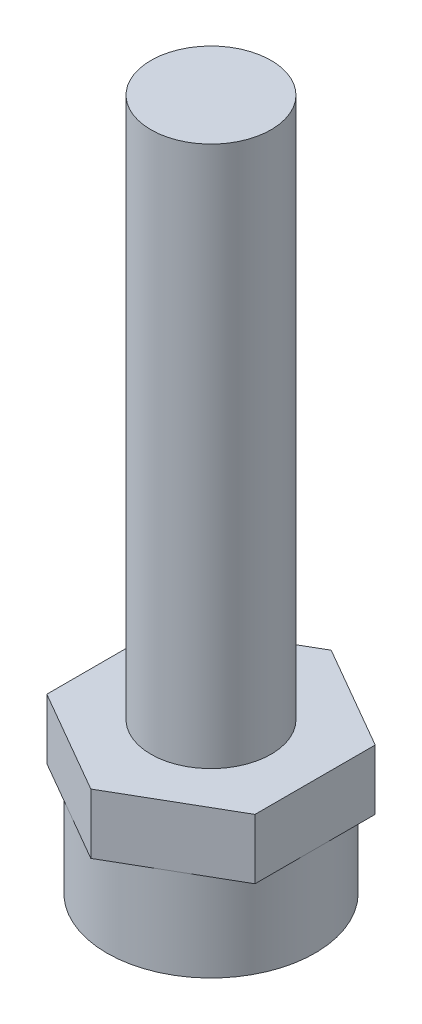
SolidWorks part; units mm, degrees
ref_plane "Front Plane" through (0, 0, 0) normal (0, 0, 1) x (1, 0, 0)
ref_plane "Top Plane" through (0, 0, 0) normal (0, 1, 0) x (1, 0, 0)
ref_plane "Right Plane" through (0, 0, 0) normal (1, 0, 0) x (0, 0, -1)
sketch "Sketch1" plane through (0, 0, 0) normal (0, 1, 0) x (1, 0, 0)
  line L0 (0, 0) -> (0, 2) construction
  line L1 (0, 2) -> (-1.7321, 1)
  line L2 (-1.7321, 1) -> (-1.7321, -1)
  line L3 (-1.7321, -1) -> (0, -2)
  line L4 (0, -2) -> (1.7321, -1)
  line L5 (1.7321, -1) -> (1.7321, 1)
  line L6 (1.7321, 1) -> (0, 2)
  circle A0 centre (0, 0) radius 1
  circle A1 centre (0, 0) radius 1.7321
  dimension "D1" = 2
  dimension "D2" = 2
extrude "Boss-Extrude1" add sketch "Sketch1" along normal blind 10 contours A0 region at (0, 0, 0)
extrude "Boss-Extrude2" add sketch "Sketch1<4>" against normal blind 1.5 contours A0 A1 | A0 region at (0, 0, -1.6831) region at (0, 0, 0)
sketch "Sketch1<4>" plane through (0, 0, 0) normal (0, 1, 0) x (1, 0, 0) same geometry as "Sketch1"
extrude "Boss-Extrude3" add sketch "Sketch1<5>" along normal blind 1 separate body contours A0 A1 | A1 L4 L5 | A1 L3 L4 | A1 L2 L3 | A1 L1 L2 | L0 A1 L6 | A1 L0 L1 | A1 L5 L6 region at (0.4356, 0, -1.6257) region at (-0.2226, 0, -1.7902) region at (0.2226, 0, -1.7902) region at (1.5503, 0, -0.8951) region at (-1.5503, 0, -0.8951) region at (1.5503, 0, 0.8951) region at (-1.5503, 0, 0.8951) region at (0, 0, 1.7902)
sketch "Sketch1<5>" plane through (0, 0, 0) normal (0, 1, 0) x (1, 0, 0) same geometry as "Sketch1"
